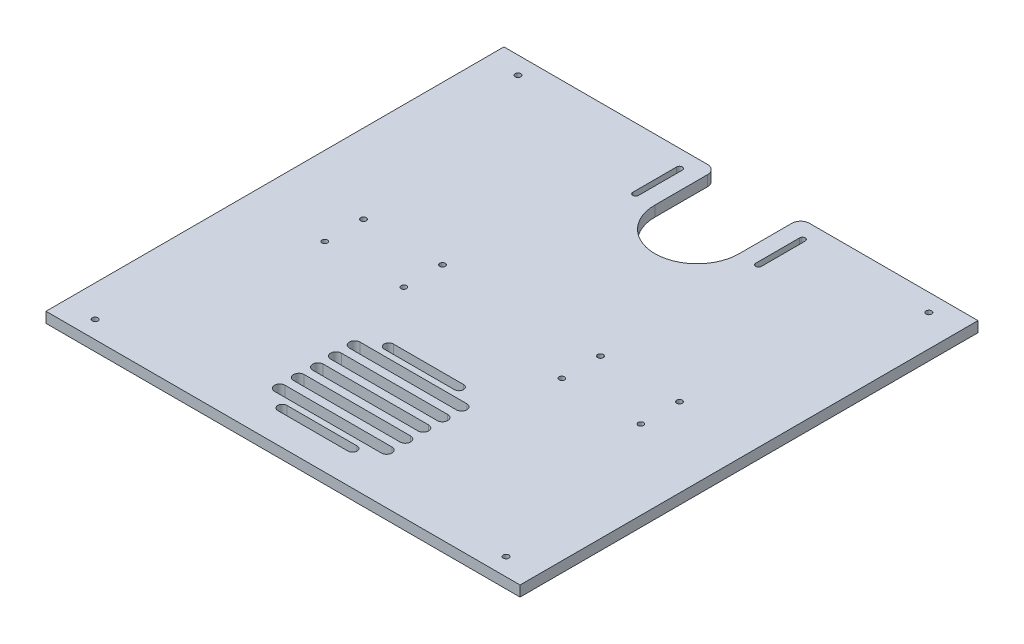
SolidWorks part; units mm, degrees
ref_plane "Front Plane" through (0, 0, 0) normal (0, 0, 1) x (1, 0, 0)
ref_plane "Top Plane" through (0, 0, 0) normal (0, 1, 0) x (1, 0, 0)
ref_plane "Right Plane" through (0, 0, 0) normal (1, 0, 0) x (0, 0, -1)
sketch "Sketch1" plane through (0, 0, 0) normal (0, 1, 0) x (1, 0, 0)
  line L0 (-145, 120) -> (125, 120)
  line L1 (-145, 120) -> (-145, -100.8)
  line L3 (125, 120) -> (125, -100.8)
  line L4 (0, 0) -> (0, 120) construction
  line L7 (-145, -100.8) -> (-145, -140.8)
  line L8 (-145, -140.8) -> (125, -140.8)
  line L9 (125, -100.8) -> (125, -140.8)
  circle A0 centre (-100, -5) radius 1.6
  circle A2 centre (80, -5) radius 1.6
  circle A3 centre (-55, -5) radius 1.6
  circle A4 centre (35, -5) radius 1.6
  circle A6 centre (-55, -5) radius 1.125 construction
  dimension "D1" = 3.2
  dimension "D2" = 40
extrude "Boss-Extrude1" add sketch "Sketch1" along normal blind 6
sketch "Sketch3" plane through (0, 6, 0) normal (0, 1, 0) x (1, 0, 0)
  line L3 (0, 120) -> (0, 0) construction
  line L4 (125, 120) -> (-145, 120) construction
  line L5 (-24, 85) -> (-24, 120)
  line L60 (24, 85) -> (24, 120)
  line L61 (24, 120) -> (-24, 120)
  arc A0 (-24, 85) -> (24, 85) centre (0, 85) ccw
  dimension "D1" = 24
  dimension "D2" = 35
extrude "Cut-Extrude1" cut sketch "Sketch3" against normal through all both and the other way through all
sketch "Sketch4" plane through (0, 0, 0) normal (0, -1, 0) x (1, 0, 0)
  circle A0 centre (107, -110) radius 1.6
  circle A1 centre (-127, -110) radius 1.6
  circle A2 centre (107, 130.8) radius 1.6
  circle A3 centre (-127, 130.8) radius 1.6
extrude "Cut-Extrude2" cut sketch "Sketch4" against normal blind 10
sketch "Sketch5" plane through (0, 6, 0) normal (0, 1, 0) x (1, 0, 0)
  line L0 (24, 85) -> (24, 120) construction
  line L1 (-24, 120) -> (-24, 85) construction
  line L2 (24, 85) -> (24, 120) construction
  line L3 (-24, 120) -> (-24, 85) construction
  line L4 (-24, 120) -> (24, 120) construction
  line L5 (-35, 120) -> (-35, 85) construction
  line L6 (-24, 120) -> (-145, 120) construction
  line L7 (-35, 110) -> (-35, 85) construction
  line L8 (-33.4, 110) -> (-33.4, 85)
  line L9 (-36.6, 110) -> (-36.6, 85)
  line L10 (0, 120) -> (0, 85) construction
  line L11 (35, 120) -> (35, 85) construction
  line L12 (35, 110) -> (35, 85) construction
  line L13 (33.4, 110) -> (33.4, 85)
  line L14 (36.6, 110) -> (36.6, 85)
  arc A0 (-33.4, 110) -> (-36.6, 110) centre (-35, 110) ccw
  arc A1 (-36.6, 85) -> (-33.4, 85) centre (-35, 85) ccw
  arc A2 (33.4, 110) -> (36.6, 110) centre (35, 110) cw
  arc A3 (36.6, 85) -> (33.4, 85) centre (35, 85) cw
  point P8 (-35, 110)
  point P12 (-35, 97.5)
  point P21 (35, 97.5)
  dimension "D3" = 1.6
  dimension "D2" = 10
extrude "Cut-Extrude3" cut sketch "Sketch5" against normal blind 10
fillet "Fillet1" radius 5 2 edges at (24, 3, -120) (-24, 3, -120)
sketch "Sketch6" plane through (0, 0, 0) normal (0, -1, 0) x (1, 0, 0)
  line L0 (10, 58.0215) -> (-30, 58.0215) construction
  line L1 (-30, 63.1632) -> (10, 63.1632) construction
  line L2 (20.436, 66.5711) -> (-40.436, 66.5711) construction
  line L3 (-40.436, 72.5711) -> (20.436, 72.5711) construction
  line L4 (20.3168, 77.3259) -> (-40.3168, 77.3259) construction
  line L5 (-40.3168, 83.3259) -> (20.3168, 83.3259) construction
  line L6 (-30, 123.7773) -> (10, 123.7773) construction
  line L7 (10, 118.6356) -> (-30, 118.6356) construction
  line L8 (-40.436, 115.2277) -> (20.436, 115.2277) construction
  line L9 (20.436, 109.2277) -> (-40.436, 109.2277) construction
  line L10 (-40.3168, 104.4728) -> (20.3168, 104.4728) construction
  line L11 (20.3168, 98.4728) -> (-40.3168, 98.4728) construction
  line L12 (20, 87.8994) -> (-40, 87.8994) construction
  line L13 (-40, 93.8994) -> (20, 93.8994) construction
  line L14 (10, 58.0215) -> (-30, 58.0215)
  line L15 (-30, 63.1632) -> (10, 63.1632)
  line L16 (20.436, 66.5711) -> (-40.436, 66.5711)
  line L17 (-40.436, 72.5711) -> (20.436, 72.5711)
  line L18 (20.3168, 77.3259) -> (-40.3168, 77.3259)
  line L19 (-40.3168, 83.3259) -> (20.3168, 83.3259)
  line L20 (-30, 123.7773) -> (10, 123.7773)
  line L21 (10, 118.6356) -> (-30, 118.6356)
  line L22 (-40.436, 115.2277) -> (20.436, 115.2277)
  line L23 (20.436, 109.2277) -> (-40.436, 109.2277)
  line L24 (-40.3168, 104.4728) -> (20.3168, 104.4728)
  line L25 (20.3168, 98.4728) -> (-40.3168, 98.4728)
  line L26 (20, 87.8994) -> (-40, 87.8994)
  line L27 (-40, 93.8994) -> (20, 93.8994)
  arc A0 (-30, 63.1632) -> (-30, 58.0215) centre (-30, 60.5923) ccw construction
  arc A1 (10, 58.0215) -> (10, 63.1632) centre (10, 60.5923) ccw construction
  arc A2 (-40.436, 72.5711) -> (-40.436, 66.5711) centre (-40.436, 69.5711) ccw construction
  arc A3 (20.436, 66.5711) -> (20.436, 72.5711) centre (20.436, 69.5711) ccw construction
  arc A4 (-40.3168, 83.3259) -> (-40.3168, 77.3259) centre (-40.3168, 80.3259) ccw construction
  arc A5 (20.3168, 77.3259) -> (20.3168, 83.3259) centre (20.3168, 80.3259) ccw construction
  arc A6 (-30, 123.7773) -> (-30, 118.6356) centre (-30, 121.2064) ccw construction
  arc A7 (10, 118.6356) -> (10, 123.7773) centre (10, 121.2064) ccw construction
  arc A8 (20.436, 109.2277) -> (20.436, 115.2277) centre (20.436, 112.2277) ccw construction
  arc A9 (-40.436, 115.2277) -> (-40.436, 109.2277) centre (-40.436, 112.2277) ccw construction
  arc A10 (-40.3168, 104.4728) -> (-40.3168, 98.4728) centre (-40.3168, 101.4728) ccw construction
  arc A11 (20.3168, 98.4728) -> (20.3168, 104.4728) centre (20.3168, 101.4728) ccw construction
  arc A12 (-40, 93.8994) -> (-40, 87.8994) centre (-40, 90.8994) ccw construction
  arc A13 (20, 87.8994) -> (20, 93.8994) centre (20, 90.8994) ccw construction
  arc A14 (-30, 63.1632) -> (-30, 58.0215) centre (-30, 60.5923) ccw
  arc A15 (10, 58.0215) -> (10, 63.1632) centre (10, 60.5923) ccw
  arc A16 (-40.436, 72.5711) -> (-40.436, 66.5711) centre (-40.436, 69.5711) ccw
  arc A17 (20.436, 66.5711) -> (20.436, 72.5711) centre (20.436, 69.5711) ccw
  arc A18 (-40.3168, 83.3259) -> (-40.3168, 77.3259) centre (-40.3168, 80.3259) ccw
  arc A19 (20.3168, 77.3259) -> (20.3168, 83.3259) centre (20.3168, 80.3259) ccw
  arc A20 (-30, 123.7773) -> (-30, 118.6356) centre (-30, 121.2064) ccw
  arc A21 (10, 118.6356) -> (10, 123.7773) centre (10, 121.2064) ccw
  arc A22 (20.436, 109.2277) -> (20.436, 115.2277) centre (20.436, 112.2277) ccw
  arc A23 (-40.436, 115.2277) -> (-40.436, 109.2277) centre (-40.436, 112.2277) ccw
  arc A24 (-40.3168, 104.4728) -> (-40.3168, 98.4728) centre (-40.3168, 101.4728) ccw
  arc A25 (20.3168, 98.4728) -> (20.3168, 104.4728) centre (20.3168, 101.4728) ccw
  arc A26 (-40, 93.8994) -> (-40, 87.8994) centre (-40, 90.8994) ccw
  arc A27 (20, 87.8994) -> (20, 93.8994) centre (20, 90.8994) ccw
extrude "Cut-Extrude4" cut sketch "Sketch6" against normal blind 10 and the other way blind 10
sketch "Sketch7" plane through (0, 0, 0) normal (0, -1, 0) x (1, 0, 0)
  circle A0 centre (80, 27) radius 1.55
  circle A1 centre (35, 27) radius 1.55
  circle A2 centre (-55, 27) radius 1.55
  circle A3 centre (-100, 27) radius 1.55
extrude "Cut-Extrude5" cut sketch "Sketch7" against normal blind 10
